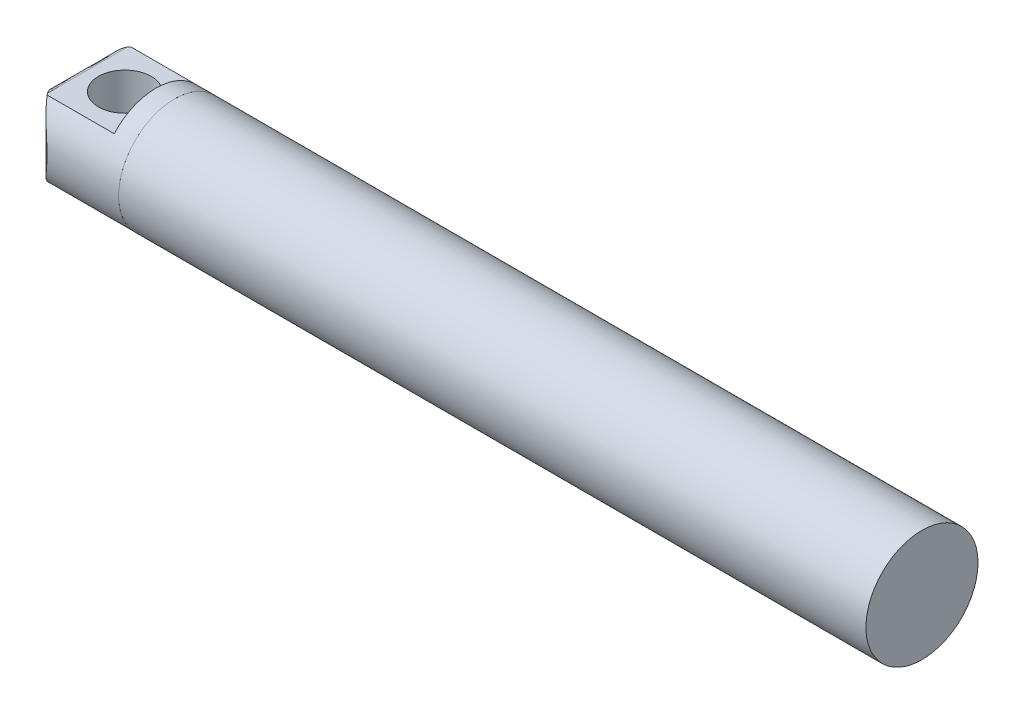
SolidWorks part; units mm, degrees
ref_plane "Front Plane" through (0, 0, 0) normal (0, 0, 1) x (1, 0, 0)
ref_plane "Top Plane" through (0, 0, 0) normal (0, 1, 0) x (1, 0, 0)
ref_plane "Right Plane" through (0, 0, 0) normal (1, 0, 0) x (0, 0, -1)
sketch "Sketch2" plane through (0, 0, 0) normal (1, 0, 0) x (0, 0, -1)
  circle A0 centre (0, 0) radius 4.5
  dimension "D1" = 9
extrude "Boss-Extrude1" add sketch "Sketch2" along normal blind 60
sketch "Sketch3" plane through (0, 0, 0) normal (-1, 0, 0) x (0, 0, 1)
  circle A1 centre (0, 0) radius 4.5
  circle A2 centre (0, 0) radius 4.5
  dimension "D1" = 0
extrude "Boss-Extrude2" add sketch "Sketch3" along normal blind 8 separate body
sketch "Sketch4" plane through (-8, 0, 0) normal (-1, 0, 0) x (0, 0, 1)
  line L1 (-3.3541, 3) -> (3.3541, 3)
  line L2 (-3.3541, 3) -> (-3.3541, -3)
  line L3 (-3.3541, -3) -> (3.3541, -3)
  line L4 (3.3541, 3) -> (3.3541, -3)
  line L5 (-3.3541, 3) -> (3.3541, -3) construction
  line L6 (-3.3541, -3) -> (3.3541, 3) construction
  circle A0 centre (0, 0) radius 4.5 construction
  circle A2 centre (0, 0) radius 4.5
  circle A3 centre (0, 0) radius 4.5
  point P0 (0, 0)
  circle M5 centre (0, 0) radius 4.5
  dimension "D1" = 6
  dimension "D2" = 0
extrude "Cut-Extrude1" cut sketch "Sketch4" against normal offset from surface (6.5 mm away) 1.5 contours L1 M5 | L3 M5 up to face at (0, 0, 4.5)
sketch "Sketch5" plane through (0, -3, 0) normal (0, -1, 0) x (1, 0, 0)
  line L0 (0, 0) -> (-8, 0) construction
  line L1 (-8, -3.3541) -> (-8, 3.3541) construction
  circle A0 centre (-4, 0) radius 2.125
  dimension "D1" = 4.25
  dimension "D2" = 4
extrude "Cut-Extrude2" cut sketch "Sketch5" against normal through all
fillet "Fillet1" [suppressed] radius 1.5
sketch "Sketch6" plane through (0, -3, 0) normal (0, -1, 0) x (1, 0, 0)
  line L0 (-8, -4.5) -> (-3.5, -4.5) construction
  line L2 (-8, 0) -> (0, 0) construction
  line L4 (-8, -3.3541) -> (-8, 3.3541) construction
  line L5 (-8, 4.5) -> (-3.5, 4.5) construction
  line L6 (-3.5, -4.5) -> (-8, -4.5)
  line L7 (-8, -4.5) -> (-8, 4.5)
  line L8 (-8, 4.5) -> (-3.5, 4.5)
  line L9 (-1.5, 3.3541) -> (-8, 3.3541) construction
  arc A0 (-3.5, -4.5) -> (-3.5, 4.5) centre (-3.5, 0) cw
  point P1 (-6.5, 3.3541)
  dimension "D1" = 1.5
fillet "Fillet2" radius 1 1 edges at (-8, -3, 0) second distance 3 first distance on face at (-4, -3, -2.125)
fillet "Fillet3" radius 1 1 edges at (-8, 3, 0) second distance 3 first distance on face at (-4, 3, -2.125)
sketch "Sketch8" plane through (0, -3, 0) normal (0, -1, 0) x (1, 0, 0)
  line L0 (-8, 0) -> (0, 0) construction
  line L1 (-8, -4.5) -> (-8, 4.5) construction
  line L3 (-8, 4.5) -> (-3.5, 4.5) construction
  line L4 (-3.5, -4.5) -> (-8, -4.5) construction
  line L5 (-5.75, -4.5) -> (-8, -4.5)
  line L6 (-8, -4.5) -> (-8, 4.5)
  line L7 (-8, 4.5) -> (-5.75, 4.5)
  arc A0 (-5.75, -4.5) -> (-5.75, 4.5) centre (-2.375, 0) cw
  dimension "D1" = 2.25
extrude "Cut-Extrude5" cut sketch "Sketch8" against normal through all both and the other way through all
